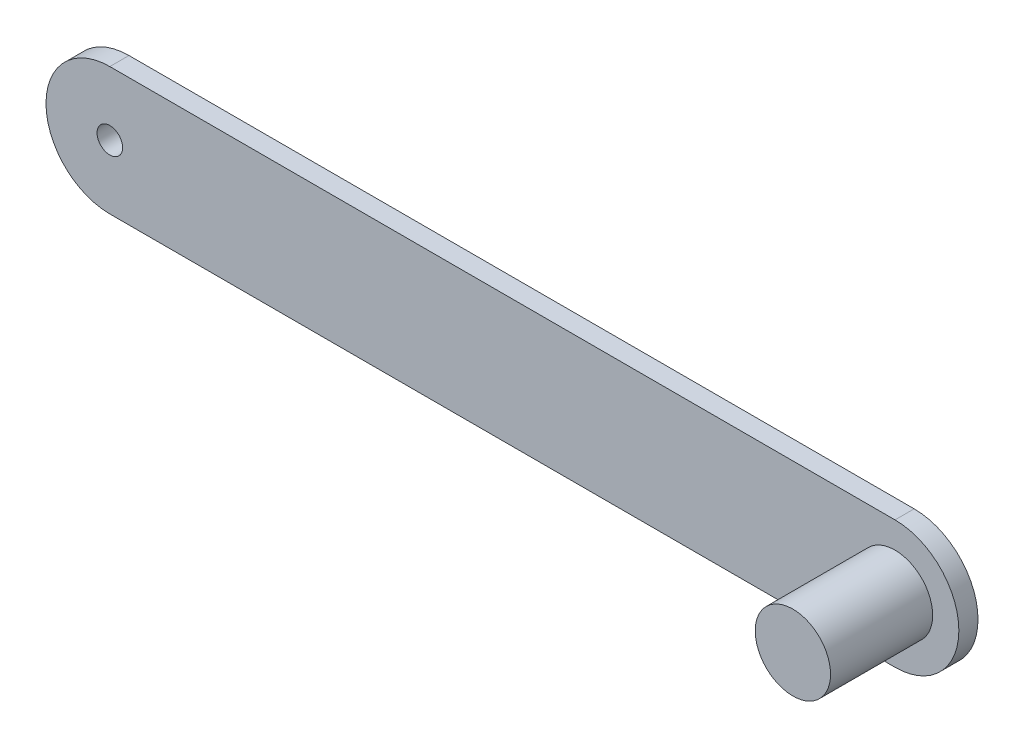
SolidWorks part; units mm, degrees
ref_plane "Front Plane" through (0, 0, 0) normal (0, 0, 1) x (1, 0, 0)
ref_plane "Top Plane" through (0, 0, 0) normal (0, 1, 0) x (1, 0, 0)
ref_plane "Right Plane" through (0, 0, 0) normal (1, 0, 0) x (0, 0, -1)
sketch "Sketch1" plane through (0, 0, 0) normal (0, 0, 1) x (1, 0, 0)
  line L0 (0, 5) -> (61.5, 5)
  line L6 (0, -5) -> (61.5, -5)
  arc A2 (0, 5) -> (0, -5) centre (0, 0) ccw
  arc A3 (61.5, -5) -> (61.5, 5) centre (61.5, 0) ccw
  dimension "D1" = 10
  dimension "D2" = 61.5
extrude "Boss-Extrude4" add sketch "Sketch1" along normal blind 1.5
sketch "Sketch4" plane through (0, 0, 1.5) normal (0, 0, 1) x (1, 0, 0)
  circle A0 centre (0, 0) radius 1
  dimension "D1" = 2
extrude "Cut-Extrude1" cut sketch "Sketch4" against normal through all
sketch "Sketch5" plane through (0, 0, 1.5) normal (0, 0, 1) x (1, 0, 0)
  circle A0 centre (61.5, 0) radius 2.95
  arc A3 (61.5, -5) -> (61.5, 5) centre (61.5, 0) ccw construction
  dimension "D1" = 5.9
extrude "Boss-Extrude5" add sketch "Sketch5" along normal blind 8
